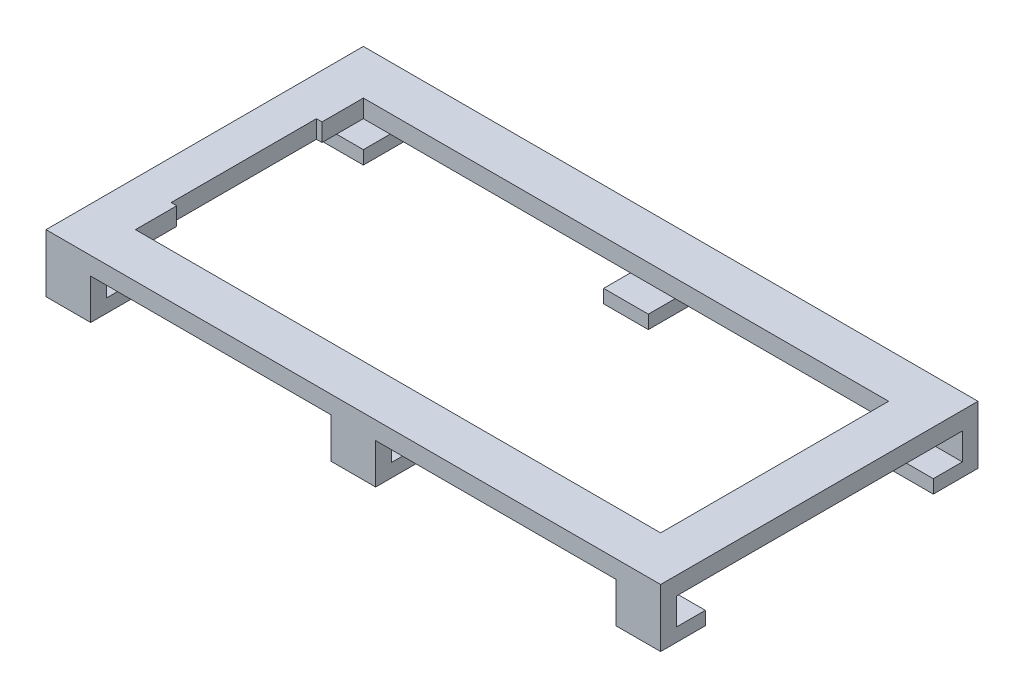
SolidWorks part; units mm, degrees
ref_plane "Alzado" through (0, 0, 0) normal (0, 0, 1) x (1, 0, 0)
ref_plane "Planta" through (0, 0, 0) normal (0, 1, 0) x (1, 0, 0)
ref_plane "Vista lateral" through (0, 0, 0) normal (1, 0, 0) x (0, 0, -1)
sketch "Croquis1" plane through (0, 0, 0) normal (0, 1, 0) x (1, 0, 0)
  line L0 (117.5, 51) -> (-117.5, 51)
  line L1 (137.5, -71) -> (-137.5, -71)
  line L2 (137.5, -71) -> (137.5, 71)
  line L3 (137.5, 71) -> (-137.5, 71)
  line L4 (-137.5, -71) -> (-137.5, 71)
  line L5 (137.5, -71) -> (-137.5, 71) construction
  line L6 (137.5, 71) -> (-137.5, -71) construction
  line L7 (-117.5, -51) -> (-117.5, 51)
  line L8 (117.5, -51) -> (-117.5, -51)
  line L9 (117.5, -51) -> (117.5, 51)
  point P0 (0, 0)
  dimension "D1" = 142
  dimension "D2" = 275
  dimension "D3" = 20
extrude "Saliente-Extruir1" add sketch "Croquis1" along normal blind 8
sketch "Croquis2" plane through (-137.5, 0, 0) normal (-1, 0, 0) x (0, 0, 1)
  line L0 (71, 0) -> (71, -18)
  line L1 (71, -18) -> (51, -18)
  line L2 (51, -18) -> (51, -12)
  line L3 (51, -12) -> (64, -12)
  line L4 (64, -12) -> (64, 0)
  line L5 (-71, 0) -> (71, 0) construction
  line L6 (64, 0) -> (71, 0)
  dimension "D1" = 7
  dimension "D2" = 6
  dimension "D3" = 20
  dimension "D4" = 18
extrude "Saliente-Extruir2" add sketch "Croquis2" against normal blind 20
mirror "Simetría1" about plane through (0, 0, 0) normal (1, 0, 0) of "Saliente-Extruir2"
mirror "Simetría2" about plane through (0, 0, 0) normal (0, 0, 1) of "Simetría1"
sketch "Croquis3" plane through (0, 8, 0) normal (0, 1, 0) x (1, 0, 0)
  line L1 (-120, 32.5) -> (-60, 32.5)
  line L2 (-120, 32.5) -> (-120, -32.5)
  line L3 (-120, -32.5) -> (-60, -32.5)
  line L4 (-60, 32.5) -> (-60, -32.5)
  point P4 (-60, 0)
  dimension "D1" = 65
  dimension "D2" = 60
  dimension "D3" = 60
extrude "Cortar-Extruir1" cut sketch "Croquis3" against normal through all
mirror "Simetría3" [suppressed] about plane through (0, 0, 0) normal (1, 0, 0)
sketch "Croquis4" plane through (0, 0, 0) normal (1, 0, 0) x (0, 0, -1)
  line L0 (-51, -18) -> (-71, -18) construction
  line L1 (-51, -12) -> (-51, -18) construction
  line L2 (-64, -12) -> (-51, -12) construction
  line L3 (-64, 0) -> (-64, -12) construction
  line L4 (-51, -18) -> (-71, -18)
  line L5 (-51, -12) -> (-51, -18)
  line L6 (-64, -12) -> (-51, -12)
  line L7 (-64, 0) -> (-64, -12)
  line L8 (-71, -18) -> (-71, 0)
  line L9 (-71, 0) -> (-64, 0)
extrude "Saliente-Extruir3" add sketch "Croquis4" along normal mid plane 20
mirror "Simetría4" about plane through (0, 0, 0) normal (0, 0, 1) of "Saliente-Extruir3"
